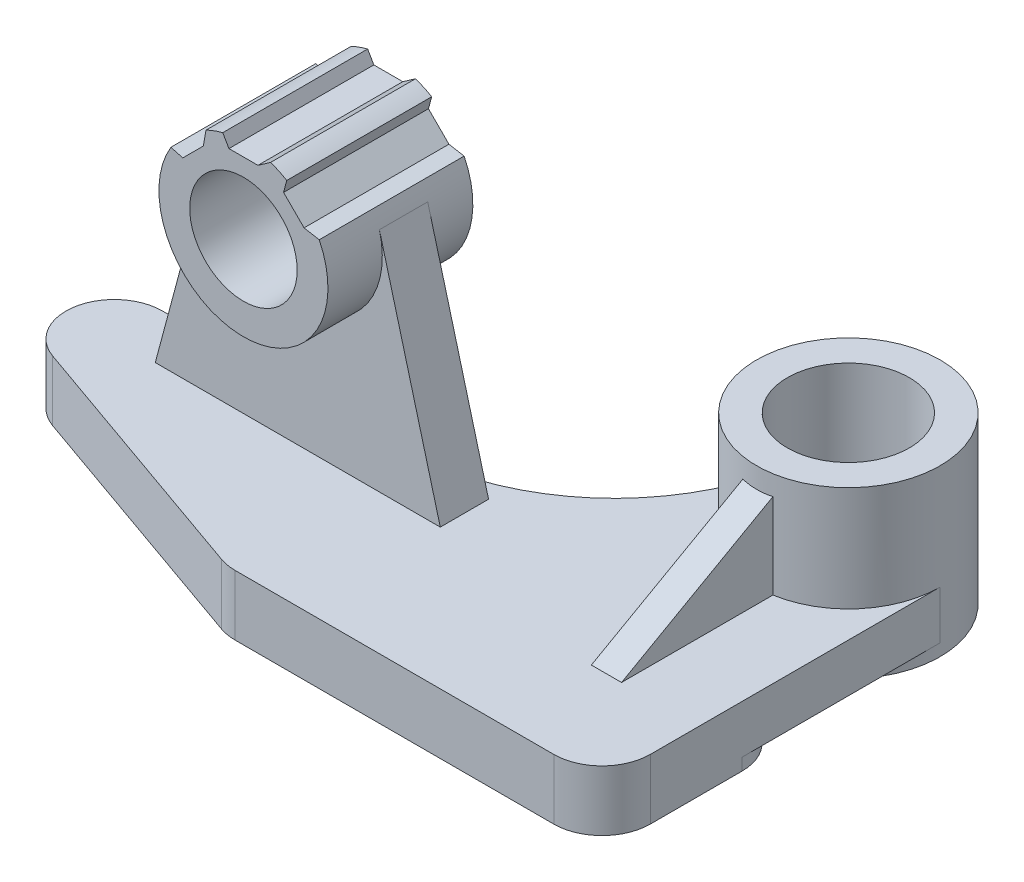
SolidWorks part; units mm, degrees
ref_plane "Front Plane" through (0, 0, 0) normal (0, 0, 1) x (1, 0, 0)
ref_plane "Top Plane" through (0, 0, 0) normal (0, 1, 0) x (1, 0, 0)
ref_plane "Right Plane" through (0, 0, 0) normal (1, 0, 0) x (0, 0, -1)
sketch "Sketch1" plane through (0, 0, 0) normal (0, 1, 0) x (1, 0, 0)
  line L0 (38, 0) -> (38, -120)
  line L1 (18, -140) -> (-114, -140)
  line L2 (-120.6381, -138.8662) -> (-228.6381, -100.8662)
  line L3 (-222, -62) -> (-124.9, -62)
  arc A0 (38, 0) -> (-37.0797, 8.3125) centre (0, 0) ccw
  arc A1 (-124.9, -62) -> (-37.0797, 8.3125) centre (-124.9, 28) ccw
  arc A2 (38, -120) -> (18, -140) centre (18, -120) cw
  arc A3 (-114, -140) -> (-120.6381, -138.8662) centre (-114, -120) cw
  arc A4 (-228.6381, -100.8662) -> (-222, -62) centre (-222, -82) cw
  dimension "D1" = 76
  dimension "D3" = 20
  dimension "D7" = 90
  dimension "D2" = 140
  dimension "D4" = 82
  dimension "D5" = 222
  dimension "D6" = 114
extrude "Boss-Extrude1" add sketch "Sketch1" along normal blind 20
sketch "Sketch2" plane through (0, 0, 0) normal (0, -1, 0) x (1, 0, 0)
  line L4 (38, 0) -> (38, 120)
  line L5 (18, 140) -> (-114, 140)
  line L6 (-120.6381, 138.8662) -> (-228.6381, 100.8662)
  line L7 (-222, 62) -> (-124.9, 62)
  line L8 (38, 82) -> (38, 120)
  line L9 (18, 140) -> (-114, 140)
  line L10 (-120.6381, 138.8662) -> (-228.6381, 100.8662)
  line L11 (-222, 62) -> (18, 62)
  arc A0 (18, 62) -> (38, 82) centre (18, 82) ccw
  arc A5 (-37.0797, -8.3125) -> (38, 0) centre (0, 0) ccw
  arc A6 (38, 120) -> (18, 140) centre (18, 120) ccw
  arc A7 (-114, 140) -> (-120.6381, 138.8662) centre (-114, 120) ccw
  arc A8 (-228.6381, 100.8662) -> (-222, 62) centre (-222, 82) ccw
  arc A9 (-37.0797, -8.3125) -> (-124.9, 62) centre (-124.9, -28) ccw
  arc A11 (38, 120) -> (18, 140) centre (18, 120) ccw
  arc A12 (-114, 140) -> (-120.6381, 138.8662) centre (-114, 120) ccw
  arc A13 (-228.6381, 100.8662) -> (-222, 62) centre (-222, 82) ccw
  point P0 (55.2131, 62)
  dimension "D2" = 20
  dimension "D1" = 0
extrude "Boss-Extrude3" add sketch "Sketch2" along normal blind 5
sketch "Sketch3" plane through (0, -5, 0) normal (0, -1, 0) x (1, 0, 0)
  circle A0 centre (0, 0) radius 38
  arc A1 (-37.0797, -8.3125) -> (38, 0) centre (0, 0) ccw construction
extrude "Boss-Extrude4" add sketch "Sketch3" against normal blind 68.5
sketch "Sketch4" plane through (0, 63.5, 0) normal (0, 1, 0) x (1, 0, 0)
  circle A0 centre (0, 0) radius 25.25
  dimension "D1" = 50.5
extrude "Cut-Extrude1" cut sketch "Sketch4" against normal through all
sketch "Sketch5" plane through (0, 0, 0) normal (0, 0, 1) x (1, 0, 0)
  line L0 (-146, -980) -> (-146, 49020) construction
  line L1 (38, 63.5) -> (-38, 63.5) construction
  line L2 (-205.0103, 20) -> (-179.8074, 114.0587)
  line L3 (-228.6381, 20) -> (-120.6381, 20) construction
  line L4 (-112.1926, 114.0587) -> (-86.9897, 20)
  line L5 (-114, 20) -> (18, 20) construction
  line L6 (-86.9897, 20) -> (-205.0103, 20)
  arc A0 (-179.8074, 114.0587) -> (-112.1926, 114.0587) centre (-146, 105) cw
  point P9 (0, 0)
  point P10 (-146, 98.17)
  dimension "D2" = 75
  dimension "D3" = 70
  dimension "D1" = 146
  dimension "D4" = 41.5
extrude "Boss-Extrude5" add sketch "Sketch5" along normal blind 20 from surface starting at face at (-109.6333, 5, 62)
sketch "Sketch6" plane through (0, 0, 0) normal (0, 0, 1) x (1, 0, 0)
  circle A0 centre (-146, 105) radius 35
  arc A1 (-112.1926, 114.0587) -> (-179.8074, 114.0587) centre (-146, 105) ccw construction
extrude "Boss-Extrude6" add sketch "Sketch6" along normal blind 60 from offset 44.5
sketch "Sketch7" plane through (0, 0, 104.5) normal (0, 0, 1) x (1, 0, 0)
  circle A0 centre (-146, 105) radius 22.25
  dimension "D1" = 44.5
extrude "Cut-Extrude2" cut sketch "Sketch7" against normal up to next
sketch "Sketch8" plane through (0, 0, 104.5) normal (0, 0, 1) x (1, 0, 0)
  line L0 (-146, 105) -> (-146, 140) construction
  line L1 (-134.7691, 138.1492) -> (-140, 134.5)
  line L2 (-140, 134.5) -> (-152, 134.5)
  line L3 (-152, 134.5) -> (-154.5615, 138.9367)
  circle A0 centre (-146, 105) radius 35 construction
  arc A1 (-134.7691, 138.1492) -> (-154.5615, 138.9367) centre (-146, 105) ccw
  point P3 (-146, 134.5)
  point P8 (-137.3845, 136.3246)
  dimension "D1" = 5.5
  dimension "D2" = 12
  dimension "D3" = 30
  dimension "D4" = 17.2309
  dimension "D5" = 85.1
  dimension "D6" = 13.5696
extrude "Cut-Extrude3" cut sketch "Sketch8" against normal up to next
pattern_circular "CirPattern1" count 2 every 45 about axis through (-146, 105, 104.5) along (0, 0, 1) of "Cut-Extrude2", "Cut-Extrude3" other way count 2
sketch "Sketch9" plane through (0, 0, 0) normal (1, 0, 0) x (0, 0, -1)
  line L0 (-38, 55) -> (-100.1818, 20)
  line L1 (-38, 63.5) -> (-38, 20) construction
  line L2 (-120, 20) -> (0, 20) construction
  dimension "D1" = 35
  dimension "D2" = 150.626
rib "Rib1" sketch "Sketch9" sketch "Sketch9" thickness 12.5 extrusion direction parallel to sketch draft on no parameters "D1"=12.5
